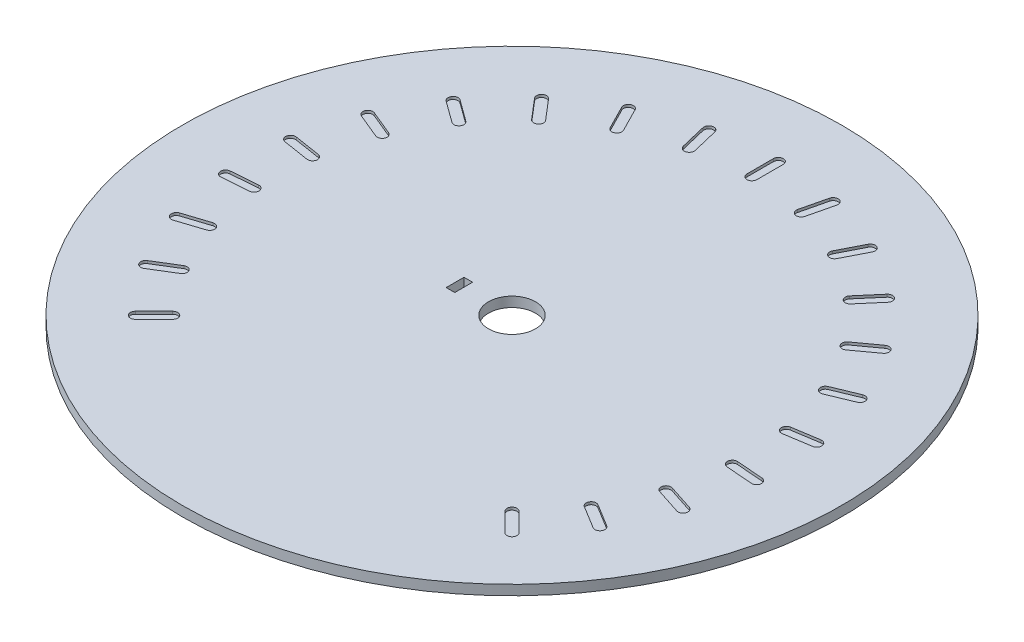
SolidWorks part; units mm, degrees
ref_plane "Front Plane" through (0, 0, 0) normal (0, 0, 1) x (1, 0, 0)
ref_plane "Top Plane" through (0, 0, 0) normal (0, 1, 0) x (1, 0, 0)
ref_plane "Right Plane" through (0, 0, 0) normal (1, 0, 0) x (0, 0, -1)
sketch "Sketch2" plane through (0, 0, 0) normal (0, 0, 1) x (1, 0, 0)
  line L0 (0, 0) -> (0, 25) construction
  line L1 (0, 0) -> (55, 0)
  line L2 (55, 0) -> (55, 20)
  line L3 (50, 25) -> (0, 25)
  line L4 (0, 25) -> (0, 23.5)
  line L5 (0, 23.5) -> (50, 23.5)
  line L6 (53.5, 20) -> (53.5, 1.5)
  line L7 (53.5, 1.5) -> (55, 1.5)
  arc A0 (55, 20) -> (50, 25) centre (50, 20) ccw
  arc A1 (50, 23.5) -> (53.5, 20) centre (50, 20) cw
  dimension "D1" = 50
  dimension "D2" = 55
  dimension "D3" = 25
  dimension "D4" = 1.5
  dimension "D5" = 1.5
  dimension "D6" = 1.5
revolve "Revolve1" add sketch "Sketch2" angle 360 about L0 region at (54.25, 2.0981, 0)
sketch "Sketch3" plane through (0, 0, 0) normal (0, 1, 0) x (1, 0, 0)
  line L1 (-8.6, 1.35) -> (-7.3, 1.35)
  line L2 (-8.6, 1.35) -> (-8.6, -1.35)
  line L3 (-8.6, -1.35) -> (-7.3, -1.35)
  line L4 (-7.3, 1.35) -> (-7.3, -1.35)
  circle A0 centre (0, 0) radius 3.55
  point P7 (-7.3, 0)
  dimension "D1" = 7.1
  dimension "D2" = 1.3
  dimension "D3" = 2.7
  dimension "D4" = 7.3
extrude "Cut-Extrude2" cut sketch "Sketch3" along normal through all
sketch "Sketch4" plane through (0, 0, 0) normal (0, 1, 0) x (1, 0, 0)
  line L0 (0, 0) -> (-35.3553, -35.3553) construction
  line L1 (0, 0) -> (35.3553, -35.3553) construction
  line L2 (-35.3553, -35.3553) -> (35.3553, -35.3553) construction
  line L3 (0, 0) -> (0, -35.3553) construction
  line L4 (-28.461, -28.461) -> (-25.6326, -25.6326) construction
  line L5 (-28.9914, -27.9307) -> (-26.163, -25.1023)
  line L6 (-27.9307, -28.9914) -> (-25.1023, -26.163)
  line L7 (-34.3188, -21.0306) -> (-30.9082, -18.9406) construction
  line L8 (-34.7106, -20.3911) -> (-31.3001, -18.3011)
  line L9 (-33.9269, -21.67) -> (-30.5163, -19.5801)
  line L10 (-38.28, -12.4379) -> (-34.4758, -11.2019) construction
  line L11 (-38.5118, -11.7246) -> (-34.7076, -10.4886)
  line L12 (-38.0483, -13.1512) -> (-34.244, -11.9152)
  line L13 (-40.1259, -3.158) -> (-36.1383, -2.8441) construction
  line L14 (-40.1848, -2.4103) -> (-36.1971, -2.0965)
  line L15 (-40.0671, -3.9057) -> (-36.0794, -3.5918)
  line L16 (-39.7545, 6.2965) -> (-35.8037, 5.6707) construction
  line L17 (-39.6371, 7.0373) -> (-35.6864, 6.4115)
  line L18 (-39.8718, 5.5557) -> (-35.921, 4.93)
  line L19 (-37.1862, 15.403) -> (-33.4906, 13.8723) construction
  line L20 (-36.8991, 16.0959) -> (-33.2036, 14.5652)
  line L21 (-37.4732, 14.7101) -> (-33.7776, 13.1794)
  line L22 (-32.5629, 23.6584) -> (-29.3269, 21.3072) construction
  line L23 (-32.1221, 24.2651) -> (-28.886, 21.914)
  line L24 (-33.0038, 23.0516) -> (-29.7677, 20.7005)
  line L25 (-26.1403, 30.6063) -> (-23.5425, 27.5647) construction
  line L26 (-25.57, 31.0934) -> (-22.9722, 28.0518)
  line L27 (-26.7106, 30.1193) -> (-24.1128, 27.0776)
  line L28 (-18.2731, 35.863) -> (-16.4572, 32.299) construction
  line L29 (-17.6049, 36.2035) -> (-15.7889, 32.6395)
  line L30 (-18.9414, 35.5225) -> (-17.1254, 31.9585)
  line L31 (-9.3962, 39.1379) -> (-8.4624, 35.2484) construction
  line L32 (-8.6669, 39.313) -> (-7.7331, 35.4235)
  line L33 (-10.1255, 38.9628) -> (-9.1917, 35.0733)
  line L34 (0, 40.25) -> (0, 36.25) construction
  line L35 (0.75, 40.25) -> (0.75, 36.25)
  line L36 (-0.75, 40.25) -> (-0.75, 36.25)
  line L37 (9.3962, 39.1379) -> (8.4624, 35.2484) construction
  line L38 (10.1255, 38.9628) -> (9.1917, 35.0733)
  line L39 (8.6669, 39.313) -> (7.7331, 35.4235)
  line L40 (18.2731, 35.863) -> (16.4572, 32.299) construction
  line L41 (18.9414, 35.5225) -> (17.1254, 31.9585)
  line L42 (17.6049, 36.2035) -> (15.7889, 32.6395)
  line L43 (26.1403, 30.6063) -> (23.5425, 27.5647) construction
  line L44 (26.7106, 30.1193) -> (24.1128, 27.0776)
  line L45 (25.57, 31.0934) -> (22.9722, 28.0518)
  line L46 (32.5629, 23.6584) -> (29.3269, 21.3072) construction
  line L47 (33.0038, 23.0516) -> (29.7677, 20.7005)
  line L48 (32.1221, 24.2651) -> (28.886, 21.914)
  line L49 (37.1862, 15.403) -> (33.4906, 13.8723) construction
  line L50 (37.4732, 14.7101) -> (33.7776, 13.1794)
  line L51 (36.8991, 16.0959) -> (33.2036, 14.5652)
  line L52 (39.7545, 6.2965) -> (35.8037, 5.6707) construction
  line L53 (39.8718, 5.5557) -> (35.921, 4.93)
  line L54 (39.6371, 7.0373) -> (35.6864, 6.4115)
  line L55 (40.1259, -3.158) -> (36.1383, -2.8441) construction
  line L56 (40.0671, -3.9057) -> (36.0794, -3.5918)
  line L57 (40.1848, -2.4103) -> (36.1971, -2.0965)
  line L58 (38.28, -12.4379) -> (34.4758, -11.2019) construction
  line L59 (38.0483, -13.1512) -> (34.244, -11.9152)
  line L60 (38.5118, -11.7246) -> (34.7076, -10.4886)
  line L61 (34.3188, -21.0306) -> (30.9082, -18.9406) construction
  line L62 (33.9269, -21.67) -> (30.5163, -19.5801)
  line L63 (34.7106, -20.3911) -> (31.3001, -18.3011)
  line L64 (28.461, -28.461) -> (25.6326, -25.6326) construction
  line L65 (27.9307, -28.9914) -> (25.1023, -26.163)
  line L66 (28.9914, -27.9307) -> (26.163, -25.1023)
  circle A0 centre (0, 0) radius 41
  circle A1 centre (0, 0) radius 50 construction
  arc A2 (-28.9914, -27.9307) -> (-27.9307, -28.9914) centre (-28.461, -28.461) ccw
  arc A3 (-25.1023, -26.163) -> (-26.163, -25.1023) centre (-25.6326, -25.6326) ccw
  arc A4 (-34.7106, -20.3911) -> (-33.9269, -21.67) centre (-34.3188, -21.0306) ccw
  arc A5 (-30.5163, -19.5801) -> (-31.3001, -18.3011) centre (-30.9082, -18.9406) ccw
  arc A6 (-38.5118, -11.7246) -> (-38.0483, -13.1512) centre (-38.28, -12.4379) ccw
  arc A7 (-34.244, -11.9152) -> (-34.7076, -10.4886) centre (-34.4758, -11.2019) ccw
  arc A8 (-40.1848, -2.4103) -> (-40.0671, -3.9057) centre (-40.1259, -3.158) ccw
  arc A9 (-36.0794, -3.5918) -> (-36.1971, -2.0965) centre (-36.1383, -2.8441) ccw
  arc A10 (-39.6371, 7.0373) -> (-39.8718, 5.5557) centre (-39.7545, 6.2965) ccw
  arc A11 (-35.921, 4.93) -> (-35.6864, 6.4115) centre (-35.8037, 5.6707) ccw
  arc A12 (-36.8991, 16.0959) -> (-37.4732, 14.7101) centre (-37.1862, 15.403) ccw
  arc A13 (-33.7776, 13.1794) -> (-33.2036, 14.5652) centre (-33.4906, 13.8723) ccw
  arc A14 (-32.1221, 24.2651) -> (-33.0038, 23.0516) centre (-32.5629, 23.6584) ccw
  arc A15 (-29.7677, 20.7005) -> (-28.886, 21.914) centre (-29.3269, 21.3072) ccw
  arc A16 (-25.57, 31.0934) -> (-26.7106, 30.1193) centre (-26.1403, 30.6063) ccw
  arc A17 (-24.1128, 27.0776) -> (-22.9722, 28.0518) centre (-23.5425, 27.5647) ccw
  arc A18 (-17.6049, 36.2035) -> (-18.9414, 35.5225) centre (-18.2731, 35.863) ccw
  arc A19 (-17.1254, 31.9585) -> (-15.7889, 32.6395) centre (-16.4572, 32.299) ccw
  arc A20 (-8.6669, 39.313) -> (-10.1255, 38.9628) centre (-9.3962, 39.1379) ccw
  arc A21 (-9.1917, 35.0733) -> (-7.7331, 35.4235) centre (-8.4624, 35.2484) ccw
  arc A22 (0.75, 40.25) -> (-0.75, 40.25) centre (0, 40.25) ccw
  arc A23 (-0.75, 36.25) -> (0.75, 36.25) centre (0, 36.25) ccw
  arc A24 (10.1255, 38.9628) -> (8.6669, 39.313) centre (9.3962, 39.1379) ccw
  arc A25 (7.7331, 35.4235) -> (9.1917, 35.0733) centre (8.4624, 35.2484) ccw
  arc A26 (18.9414, 35.5225) -> (17.6049, 36.2035) centre (18.2731, 35.863) ccw
  arc A27 (15.7889, 32.6395) -> (17.1254, 31.9585) centre (16.4572, 32.299) ccw
  arc A28 (26.7106, 30.1193) -> (25.57, 31.0934) centre (26.1403, 30.6063) ccw
  arc A29 (22.9722, 28.0518) -> (24.1128, 27.0776) centre (23.5425, 27.5647) ccw
  arc A30 (33.0038, 23.0516) -> (32.1221, 24.2651) centre (32.5629, 23.6584) ccw
  arc A31 (28.886, 21.914) -> (29.7677, 20.7005) centre (29.3269, 21.3072) ccw
  arc A32 (37.4732, 14.7101) -> (36.8991, 16.0959) centre (37.1862, 15.403) ccw
  arc A33 (33.2036, 14.5652) -> (33.7776, 13.1794) centre (33.4906, 13.8723) ccw
  arc A34 (39.8718, 5.5557) -> (39.6371, 7.0373) centre (39.7545, 6.2965) ccw
  arc A35 (35.6864, 6.4115) -> (35.921, 4.93) centre (35.8037, 5.6707) ccw
  arc A36 (40.0671, -3.9057) -> (40.1848, -2.4103) centre (40.1259, -3.158) ccw
  arc A37 (36.1971, -2.0965) -> (36.0794, -3.5918) centre (36.1383, -2.8441) ccw
  arc A38 (38.0483, -13.1512) -> (38.5118, -11.7246) centre (38.28, -12.4379) ccw
  arc A39 (34.7076, -10.4886) -> (34.244, -11.9152) centre (34.4758, -11.2019) ccw
  arc A40 (33.9269, -21.67) -> (34.7106, -20.3911) centre (34.3188, -21.0306) ccw
  arc A41 (31.3001, -18.3011) -> (30.5163, -19.5801) centre (30.9082, -18.9406) ccw
  arc A42 (27.9307, -28.9914) -> (28.9914, -27.9307) centre (28.461, -28.461) ccw
  arc A43 (26.163, -25.1023) -> (25.1023, -26.163) centre (25.6326, -25.6326) ccw
  point P10 (-27.0468, -27.0468)
  point P20 (-32.6135, -19.9856)
  point P27 (-36.3779, -11.8199)
  point P34 (-38.1321, -3.0011)
  point P41 (-37.7791, 5.9836)
  point P48 (-35.3384, 14.6376)
  point P55 (-30.9449, 22.4828)
  point P62 (-24.8414, 29.0855)
  point P69 (-17.3651, 34.081)
  point P76 (-8.9293, 37.1931)
  point P83 (0, 38.25)
  point P90 (8.9293, 37.1931)
  point P97 (17.3651, 34.081)
  point P104 (24.8414, 29.0855)
  point P111 (30.9449, 22.4828)
  point P118 (35.3384, 14.6376)
  point P125 (37.7791, 5.9836)
  point P132 (38.1321, -3.0011)
  point P139 (36.3779, -11.8199)
  point P146 (32.6135, -19.9856)
  point P153 (27.0468, -27.0468)
  point P158 (0, 0)
  dimension "D1" = 82
  dimension "D2" = 270
  dimension "D3" = 1.5
  dimension "D4" = 4
  dimension "D5" = 21
extrude "Cut-Extrude4" cut sketch "Sketch4" against normal blind 0.4 from surface contours L6 A3 L5 A2 | L9 A5 L8 A4 | L12 A7 L11 A6 | L18 A11 L17 A10 | L21 A13 L20 A12 | L15 A9 L14 A8 | L24 A15 L23 A14 | L27 A17 L26 A16 | L30 A19 L29 A18 | L33 A21 L32 A20 | L36 A23 L35 A22 | L39 A25 L38 A24 | L42 A27 L41 A26 | L45 A29 L44 A28 | L48 A31 L47 A30 | L51 A33 L50 A32 | L54 A35 L53 A34 | L60 A39 L59 A38 | L57 A37 L56 A36 | L63 A41 L62 A40 | L66 A43 L65 A42 region at (27.0468, 0, 27.0468) region at (32.6135, 0, 19.9856) region at (36.3779, 0, 11.8199) region at (38.1321, 0, 3.0011) region at (37.7791, 0, -5.9836) region at (35.3384, 0, -14.6376) region at (30.9449, 0, -22.4828) region at (24.8414, 0, -29.0855) region at (17.3651, 0, -34.081) region at (8.9293, 0, -37.1931) region at (0, 0, -38.25) region at (-8.9293, 0, -37.1931) region at (-17.3651, 0, -34.081) region at (-24.8414, 0, -29.0855) region at (-30.9449, 0, -22.4828) region at (-35.3384, 0, -14.6376) region at (-37.7791, 0, -5.9836) region at (-38.1321, 0, 3.0011) region at (-36.3779, 0, 11.8199) region at (-32.6135, 0, 19.9856) region at (-27.0468, 0, 27.0468) starting at face at (-7.95, 25, 0)
sketch "Sketch8" plane through (0, 0, 0) normal (0, 0, 1) x (1, 0, 0)
  line L0 (0, 20) -> (0, 1.5) construction
  line L1 (55, 20) -> (-55, 20) construction
  line L2 (-55, 1.5) -> (55, 1.5) construction
  circle A0 centre (0, 10.75) radius 2.5
  circle A1 centre (0, 10.75) radius 4
  dimension "D1" = 5
  dimension "D2" = 1.5
ref_plane "Plane1" through (0, 0, -60) normal (0, 0, 1) x (1, 0, 0)
extrude "Boss-Extrude1" add sketch "Sketch8" along normal up to next draft 25 from surface draft outward yes starting at plane "Plane1"
extrude "Cut-Extrude7" cut sketch "Sketch8<2>" along normal up to next from surface contours L0 A0 | A0 L0 region at (1.061, 10.75, 0) region at (-1.061, 10.75, 0) starting at face at (4, 10.75, -60)
sketch "Sketch8<2>" plane through (0, 0, 0) normal (0, 0, 1) x (1, 0, 0) same geometry as "Sketch8"
fillet "Fillet1" radius 4 2 edges at (6.4737, 11.4351, -54.6177) (2.4337, 11.322, -53.4446)
sketch "Sketch11" plane through (0, 0, 0) normal (0, 1, 0) x (1, 0, 0)
  circle A0 centre (0, 0) radius 50
  circle A1 centre (0, 0) radius 49.8
  dimension "D1" = 100
  dimension "D2" = 0.2
extrude "Cut-Extrude9" cut sketch "Sketch11" against normal through all both and the other way through all flip side to cut contours A1 region at (0, 0, 0)
